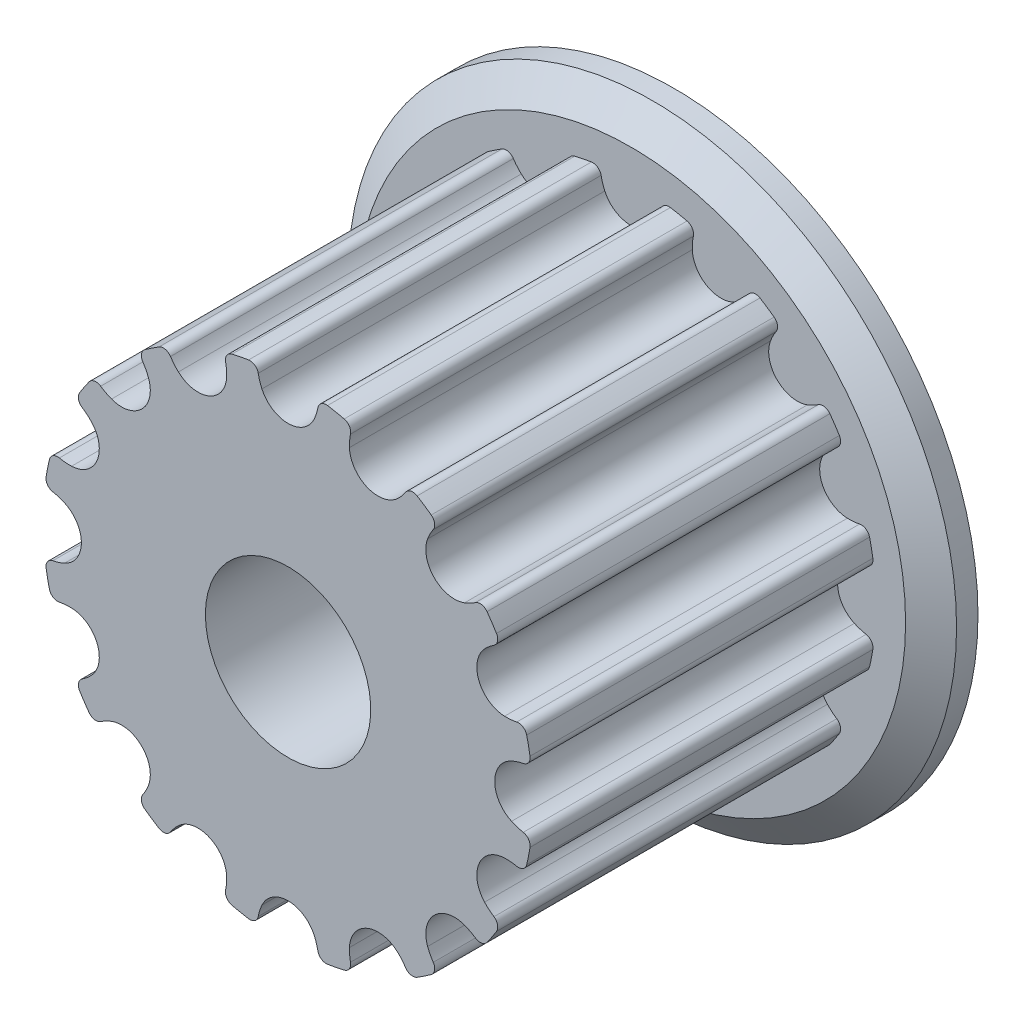
SolidWorks part; units mm, degrees
ref_plane "Front Plane" through (0, 0, 0) normal (0, 0, 1) x (1, 0, 0)
ref_plane "Top Plane" through (0, 0, 0) normal (0, 1, 0) x (1, 0, 0)
ref_plane "Right Plane" through (0, 0, 0) normal (1, 0, 0) x (0, 0, -1)
sketch "Sketch1" plane through (0, 0, 0) normal (0, 0, 1) x (1, 0, 0)
  line L1 (-2.553, 6.1245) -> (2.553, 6.1245) construction
  line L4 (0, 0) -> (0, 6.1245) construction
  line L5 (0, 6.1245) -> (0, 12.0677) construction
  line L6 (0, 7.6455) -> (2.9417, 7.0569) construction
  line L7 (2.9417, 7.0569) -> (3.8741, 6.6682) construction
  line L8 (2.9417, 7.0569) -> (2.553, 6.1245) construction
  line L9 (-2.9417, 7.0569) -> (-2.553, 6.1245) construction
  line L10 (-2.7951, 6.7052) -> (-3.7579, 9.015)
  line L11 (-3.7579, 9.015) -> (3.7579, 9.015)
  line L12 (3.7579, 9.015) -> (2.7951, 6.7052)
  circle A0 centre (0, 0) radius 7.6455 construction
  circle A1 centre (0, 0) radius 9.015 construction
  circle A2 centre (0, 0) radius 7.2645 construction
  arc A3 (-0.7739, 6.6229) -> (0.7739, 6.6229) centre (0, 6.9745) ccw
  arc A4 (-0.7739, 6.6229) -> (-0.8836, 6.9694) centre (0.61, 7.2516) cw
  arc A5 (-2.7951, 6.7052) -> (-1.1695, 7.1697) centre (0, 0) cw
  arc A6 (-0.8836, 6.9694) -> (-1.1695, 7.1697) centre (-1.1292, 6.923) ccw
  arc A7 (2.7951, 6.7052) -> (1.1695, 7.1697) centre (0, 0) ccw
  arc A8 (0.8836, 6.9694) -> (1.1695, 7.1697) centre (1.1292, 6.923) cw
  arc A9 (0.7739, 6.6229) -> (0.8836, 6.9694) centre (-0.61, 7.2516) ccw
  point P6 (0, 20.9083)
  point P11 (0, 7.6455)
  point P13 (0, 9.015)
  point P14 (0, 7.2645)
  dimension "D1" = 8.8406
  dimension "D2" = 4.4222
sketch "Sketch2" plane through (0, 0, 0) normal (1, 0, 0) x (0, 0, -1)
  line L0 (-8.775, 2.3812) -> (8.775, 2.3812)
  line L1 (-8.775, 2.3812) -> (-8.775, 9.015)
  line L2 (-3.29, 9.015) -> (-8.775, 9.015)
  line L3 (-3.925, 2.3813) -> (-3.925, 9.015) construction
  line L4 (-3.925, 9.015) -> (-2.655, 9.015) construction
  line L5 (-2.655, 9.015) -> (-2.655, 7.2645) construction
  line L6 (-2.655, 7.2645) -> (7.505, 7.2645)
  line L7 (7.505, 7.2645) -> (7.505, 9.015) construction
  line L8 (7.505, 9.015) -> (8.775, 9.015) construction
  line L9 (8.775, 9.015) -> (8.775, 2.3812)
  line L10 (-8.775, 0) -> (8.775, 0) construction
  line L11 (8.14, 9.015) -> (7.505, 8.1398)
  line L12 (-2.655, 8.1398) -> (-3.29, 9.015)
  line L14 (-2.655, 8.1398) -> (-2.655, 7.2645)
  line L15 (7.505, 7.2645) -> (7.505, 8.1398)
  line L16 (8.14, 9.015) -> (8.775, 9.015)
  arc A0 (-2.655, 8.1398) -> (-3.29, 9.015) centre (-3.5757, 8.1398) ccw construction
  arc A1 (7.505, 8.1398) -> (8.14, 9.015) centre (8.4257, 8.1398) cw construction
  point P12 (-2.655, 8.1398)
  point P14 (-3.29, 9.015)
  point P20 (7.505, 8.1398)
  point P21 (8.14, 9.015)
  point P25 (7.505, 0)
  point P26 (-2.655, 0)
  dimension "OA" = 17.55
  dimension "Bore" = 4.7625
  dimension "Outside Width" = 11.43
  dimension "Inside Width" = 10.16
revolve "Revolve1" add sketch "Sketch2" angle 360 mid plane about L10
sketch "Sketch3" plane through (0, 0, 0) normal (0, 0, 1) x (1, 0, 0)
  line L6 (3.7579, 9.015) -> (-3.7579, 9.015)
  line L7 (2.7951, 6.7052) -> (3.7579, 9.015)
  line L8 (-3.7579, 9.015) -> (-2.7951, 6.7052)
  line L9 (3.7579, 9.015) -> (-3.7579, 9.015)
  line L10 (2.7951, 6.7052) -> (3.7579, 9.015)
  line L11 (-3.7579, 9.015) -> (-2.7951, 6.7052)
  arc A8 (2.7951, 6.7052) -> (1.1695, 7.1697) centre (0, 0) ccw
  arc A9 (1.1695, 7.1697) -> (0.8836, 6.9694) centre (1.1292, 6.923) ccw
  arc A10 (0.7739, 6.6229) -> (0.8836, 6.9694) centre (-0.61, 7.2516) ccw
  arc A11 (-0.7739, 6.6229) -> (0.7739, 6.6229) centre (0, 6.9745) ccw
  arc A12 (-0.8836, 6.9694) -> (-0.7739, 6.6229) centre (0.61, 7.2516) ccw
  arc A13 (-0.8836, 6.9694) -> (-1.1695, 7.1697) centre (-1.1292, 6.923) ccw
  arc A14 (-1.1695, 7.1697) -> (-2.7951, 6.7052) centre (0, 0) ccw
  arc A15 (2.7951, 6.7052) -> (1.1695, 7.1697) centre (0, 0) ccw
  arc A16 (1.1695, 7.1697) -> (0.8836, 6.9694) centre (1.1292, 6.923) ccw
  arc A17 (0.7739, 6.6229) -> (0.8836, 6.9694) centre (-0.61, 7.2516) ccw
  arc A18 (-0.7739, 6.6229) -> (0.7739, 6.6229) centre (0, 6.9745) ccw
  arc A19 (-0.8836, 6.9694) -> (-0.7739, 6.6229) centre (0.61, 7.2516) ccw
  arc A20 (-0.8836, 6.9694) -> (-1.1695, 7.1697) centre (-1.1292, 6.923) ccw
  arc A21 (-1.1695, 7.1697) -> (-2.7951, 6.7052) centre (0, 0) ccw
  dimension "D1" = 0
extrude "Cut-Extrude1" cut sketch "Sketch3" against normal up to vertex (7.505 mm away) from vertex up to point (0, 7.2645, -7.505) starting at point (0, 7.2645, 2.655)
pattern_circular "CirPattern1" count 16 over 360 about axis through (0, 0, 8.775) along (0, 0, 1) of "Cut-Extrude1"
sketch "Sketch4" plane through (0, 0, 0) normal (1, 0, 0) x (0, -1, 0)
  line L0 (0, -2.655) -> (0, -8.775) construction
  line L1 (-2.3812, -8.775) -> (2.3812, -8.775) construction
  line L2 (8.1398, -2.655) -> (-8.1398, -2.655) construction
  circle A0 centre (0, -5.715) radius 1.7526
extrude "Cut-Extrude2" cut sketch "Sketch4" along normal through all
ref_plane "Plane1" through (0, 0, 5.715) normal (0, 0, 1) x (1, 0, 0)
sketch "Sketch5" plane through (0, 0, 5.715) normal (0, 0, 1) x (1, 0, 0)
  line L0 (0, 0) -> (0, 9.015) construction
  line L1 (2.3812, -1.3716) -> (2.3812, 0)
  line L2 (2.7622, -1.7526) -> (8.462, -1.7526)
  line L3 (2.3812, 0) -> (9.015, 0) construction
  line L4 (2.3812, 0) -> (8.843, 0)
  line L5 (8.843, 0) -> (8.843, -1.3716)
  line L6 (2.7622, -1.7526) -> (2.3812, -1.3716)
  line L7 (8.843, -1.3716) -> (8.462, -1.7526)
  circle A0 centre (0, 0) radius 9.015 construction
  circle A1 centre (0, 0) radius 2.3812 construction
  point P2 (2.3812, -1.7526)
  point P11 (8.843, -1.7526)
revolve "Revolve2" add sketch "Sketch5" angle 360 mid plane about L4
sketch "Sketch6" plane through (8.843, 5.3841, 0) normal (-1, 0, 0) x (0, -1, 0)
  line L1 (5.3841, 6.7269) -> (4.5078, 6.2209)
  line L2 (4.5078, 6.2209) -> (4.5078, 5.2091)
  line L3 (4.5078, 5.2091) -> (5.3841, 4.7031)
  line L4 (5.3841, 4.7031) -> (6.2604, 5.2091)
  line L5 (6.2604, 5.2091) -> (6.2604, 6.2209)
  line L6 (6.2604, 6.2209) -> (5.3841, 6.7269)
  circle A0 centre (5.3841, 5.715) radius 0.8763 construction
  dimension "D1" = 1.7526
extrude "Cut-Extrude3" cut sketch "Sketch6" along normal blind 1.3144
pattern_circular "CirPattern3" count 2 over 90 about axis through (0, 0, 8.775) along (0, 0, 1) of "Cut-Extrude2", "Revolve2", "Cut-Extrude3"
chamfer "Chamfer1" distance 0.2807 angle 45 2 edges at (2.3812, 0, 8.775) (9.015, 0, 8.775)
ref_axis "Center Axis 1" through (0, 0, -8.775) along (0, 0, 1)
ref_plane "Contact Plane 1" through (0, 0, 8.775) normal (0, 0, 1) x (1, 0, 0)
ref_plane "Contact Plane 2" through (0, 0, -8.775) normal (0, 0, -1) x (-1, 0, 0)
sketch "Sketch7" plane through (0, 0, 8.775) normal (0, 0, 1) x (1, 0, 0)
  circle A0 centre (0, 0) radius 9.015 construction
  circle A1 centre (0, 0) radius 9.015
extrude "Cut-Extrude4" cut sketch "Sketch7" against normal up to surface (6.12 mm away)
sketch "Sketch8" plane through (0, 0, -8.775) normal (0, 0, -1) x (-1, 0, 0)
  circle A0 centre (0, 0) radius 2.45
  dimension "D1" = 4.9
extrude "Cut-Extrude5" cut sketch "Sketch8" against normal through all
equation "\"D2@Sketch1\"= \"D1@Sketch1\" / 2"
equation "\"D1@Sketch6\" = \"Set Screw@Sketch4\" / 2"
equation "\"D1@Cut-Extrude3\" = \"D1@Sketch6\"*.75"
